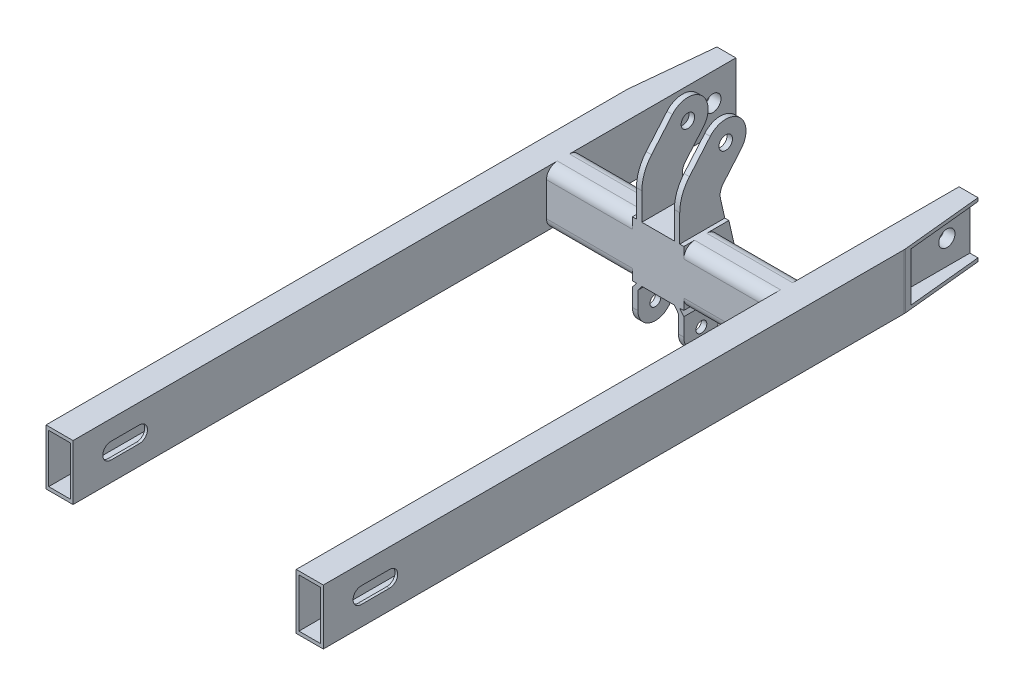
SolidWorks part; units mm, degrees
ref_plane "Спереди" through (0, 0, 0) normal (0, 0, 1) x (1, 0, 0)
ref_plane "Сверху" through (0, 0, 0) normal (0, 1, 0) x (1, 0, 0)
ref_plane "Справа" through (0, 0, 0) normal (1, 0, 0) x (0, 0, -1)
sketch "Эскиз1" plane through (0, 0, 0) normal (0, 1, 0) x (1, 0, 0)
  line L0 (0, 0) -> (14, 0)
  line L1 (0, 0) -> (0, -115)
  line L2 (14, 0) -> (20, -60)
  line L3 (20, -60) -> (20, -490)
  line L4 (20, -490) -> (0, -490)
  line L5 (0, -140) -> (-165, -140)
  line L6 (-165, -115) -> (0, -115)
  line L7 (-82.5, 71.2551) -> (-82.5, -539.2053) construction
  line L8 (0, -140) -> (0, -490)
  line L9 (-165, -140) -> (-165, -490)
  line L10 (-185, -490) -> (-165, -490)
  line L11 (-185, -60) -> (-185, -490)
  line L12 (-179, 0) -> (-185, -60)
  line L13 (-165, 0) -> (-165, -115)
  line L14 (-165, 0) -> (-179, 0)
  point P8 (-82.5, -140)
  point P15 (-82.5, -115)
  dimension "D1" = 14
  dimension "D2" = 490
  dimension "D3" = 20
  dimension "D4" = 60
  dimension "D5" = 82.5
  dimension "D6" = 350
  dimension "D7" = 25
extrude "Бобышка-Вытянуть1" add sketch "Эскиз1" along normal blind 41
fillet "Скругление4" radius 8 4 edges at (-82.5, 0, 115) (-82.5, 41, 115) (-82.5, 0, 140) (-82.5, 41, 140)
ref_plane "Плоскость1" through (-82.5, 0, 0) normal (1, 0, 0) x (0, 0, -1)
sketch "Эскиз2" plane through (-82.5, 0, 0) normal (1, 0, 0) x (0, 0, -1)
  line L0 (0, 41) -> (0, 0) construction
  line L1 (-462, 26.5) -> (-441, 26.5)
  line L2 (-462, 14.5) -> (-441, 14.5)
  line L3 (-490, 41) -> (-490, 0) construction
  circle A0 centre (-17, 20.5) radius 6
  arc A1 (-462, 26.5) -> (-462, 14.5) centre (-462, 20.5) ccw
  arc A2 (-441, 14.5) -> (-441, 26.5) centre (-441, 20.5) ccw
  point P5 (-468, 20.5)
  point P13 (-490, 20.5)
  dimension "D1" = 12
  dimension "D3" = 12
  dimension "D2" = 17
  dimension "D5" = 22
  dimension "D4" = 2
extrude "Вырез-Вытянуть1" cut sketch "Эскиз2" against normal mid plane 231
sketch "Эскиз3" plane through (0, 0, 490) normal (0, 0, 1) x (1, 0, 0)
  line L0 (2, 38.5) -> (18, 38.5)
  line L1 (-183, 38.5) -> (-167, 38.5)
  line L2 (-183, 38.5) -> (-183, 2.5)
  line L3 (-183, 2.5) -> (-167, 2.5)
  line L4 (-167, 38.5) -> (-167, 2.5)
  line L5 (-183, 38.5) -> (-167, 2.5) construction
  line L6 (-183, 2.5) -> (-167, 38.5) construction
  line L7 (2, 38.5) -> (2, 2.5)
  line L8 (2, 2.5) -> (18, 2.5)
  line L9 (18, 38.5) -> (18, 2.5)
  line L10 (2, 38.5) -> (18, 2.5) construction
  line L11 (2, 2.5) -> (18, 38.5) construction
  point P0 (-175, 20.5)
  point P1 (-175, 20.5)
  point P8 (10, 20.5)
  point P9 (10, 20.5)
  dimension "D1" = 16
  dimension "D2" = 36
  dimension "D3" = 2
extrude "Вырез-Вытянуть2" cut sketch "Эскиз3" against normal blind 400
ref_plane "Плоскость2" through (-185, 0, 0) normal (-1, 0, 0) x (0, 0, 1)
sketch "Эскиз4" plane through (-185, 0, 0) normal (-1, 0, 0) x (0, 0, 1)
  line L1 (-15, 2.5) -> (55, 2.5)
  line L2 (-15, 2.5) -> (-15, 38.5)
  line L3 (-15, 38.5) -> (55, 38.5)
  line L4 (55, 2.5) -> (55, 38.5)
  line L8 (0, 0) -> (60, 0) construction
  dimension "D1" = 5
  dimension "D2" = 36
  dimension "D3" = 2.5
  dimension "D4" = 70
extrude "Вырез-Вытянуть3" cut sketch "Эскиз4" against normal blind 12
mirror "Зеркальное отражение1" about plane through (-82.5, 0, 0) normal (1, 0, 0) of "Вырез-Вытянуть3"
fillet "Скругление5" radius 12 1 edges at (20, 20.5, 60)
fillet "Скругление6" radius 12 1 edges at (-185, 20.5, 60)
ref_plane "Плоскость3" through (-82.5, 0, 0) normal (1, 0, 0) x (0, 0, -1)
sketch "Эскиз5" plane through (-82.5, 0, 0) normal (1, 0, 0) x (0, 0, -1)
  line L0 (-140, 61.1738) -> (-140, -17)
  line L2 (-103.5471, 15.4159) -> (-114.5631, -20.7846)
  line L4 (-109.886, 55.1108) -> (-103.1806, 25.6815)
  line L6 (-132.8368, 80.6285) -> (-117.4184, 98.7273)
  line L7 (-107.7481, 63.8172) -> (-94.5816, 79.2727)
  arc A0 (-140, -17) -> (-114.5631, -20.7846) centre (-127, -17) ccw
  circle A1 centre (-127, -17) radius 4
  circle A2 centre (-106, 89) radius 5
  arc A3 (-94.5816, 79.2727) -> (-117.4184, 98.7273) centre (-106, 89) ccw
  arc A4 (-140, 61.1738) -> (-132.8368, 80.6285) centre (-110, 61.1738) cw
  arc A5 (-109.886, 55.1108) -> (-107.7481, 63.8172) centre (-100.1359, 57.3323) cw
  arc A6 (-103.5471, 15.4159) -> (-103.1806, 25.6815) centre (-122.6808, 21.2384) ccw
  dimension "D5" = 26
  dimension "D6" = 8
  dimension "D11" = 10
  dimension "D7" = 30
  dimension "D8" = 10
  dimension "D9" = 20
extrude "Бобышка-Вытянуть2" add sketch "Эскиз5" along normal mid plane 38
ref_plane "Плоскость4" through (0, 0, 140) normal (0, 0, 1) x (1, 0, 0)
sketch "Эскиз6" plane through (0, 0, 140) normal (0, 0, 1) x (1, 0, 0)
  line L0 (-82.5, 111.1717) -> (-82.5, -40.8276) construction
  line L1 (-110.2266, -4) -> (-50.5019, -4) construction
  line L2 (-98.5, 104) -> (-66.5, 104) construction
  line L3 (-98.5, 104) -> (-98.5, 41)
  line L4 (-101.5139, -4) -> (-98.5, 0)
  line L5 (-98.5, 0) -> (-101.5, 0)
  line L6 (-101.5139, -4) -> (-101.5, 0)
  line L7 (-94.5, 0) -> (-70.5, 0)
  line L8 (-101.5, 41) -> (-98.5, 41)
  line L9 (-97.5, -30) -> (-97.5, -4)
  line L10 (-101.5, -30) -> (-63.5, -30) construction
  line L11 (-97.5, -4) -> (-94.5, 0)
  line L12 (-97.5, -30) -> (-67.5, -30)
  line L13 (-70.5, 104) -> (-94.5, 104)
  line L14 (-94.5, 104) -> (-94.5, 41)
  line L15 (-94.5, 41) -> (-70.5, 41)
  line L16 (-98.5, 104) -> (-101.5, 104)
  line L17 (-101.5, 104) -> (-101.5, 41)
  line L18 (-67.5, -30) -> (-67.5, -4)
  line L19 (-63.4861, -4) -> (-63.5, 0)
  line L20 (-66.5, 0) -> (-63.5, 0)
  line L21 (-63.4861, -4) -> (-66.5, 0)
  line L22 (-67.5, -4) -> (-70.5, 0)
  line L23 (-66.5, 104) -> (-63.5, 104)
  line L24 (-63.5, 104) -> (-63.5, 41)
  line L25 (-66.5, 104) -> (-66.5, 41)
  line L26 (-63.5, 41) -> (-66.5, 41)
  line L27 (-70.5, 104) -> (-70.5, 41)
  point P25 (-82.5, 104)
  point P30 (-82.5, -30)
  point P34 (-82.5, 0)
  point P35 (-82.5, 0)
  point P40 (-82.5, 41)
  dimension "D1" = 26
  dimension "D4" = 4
  dimension "D5" = 4
extrude "Вырез-Вытянуть4" cut sketch "Эскиз6" against normal blind 68
